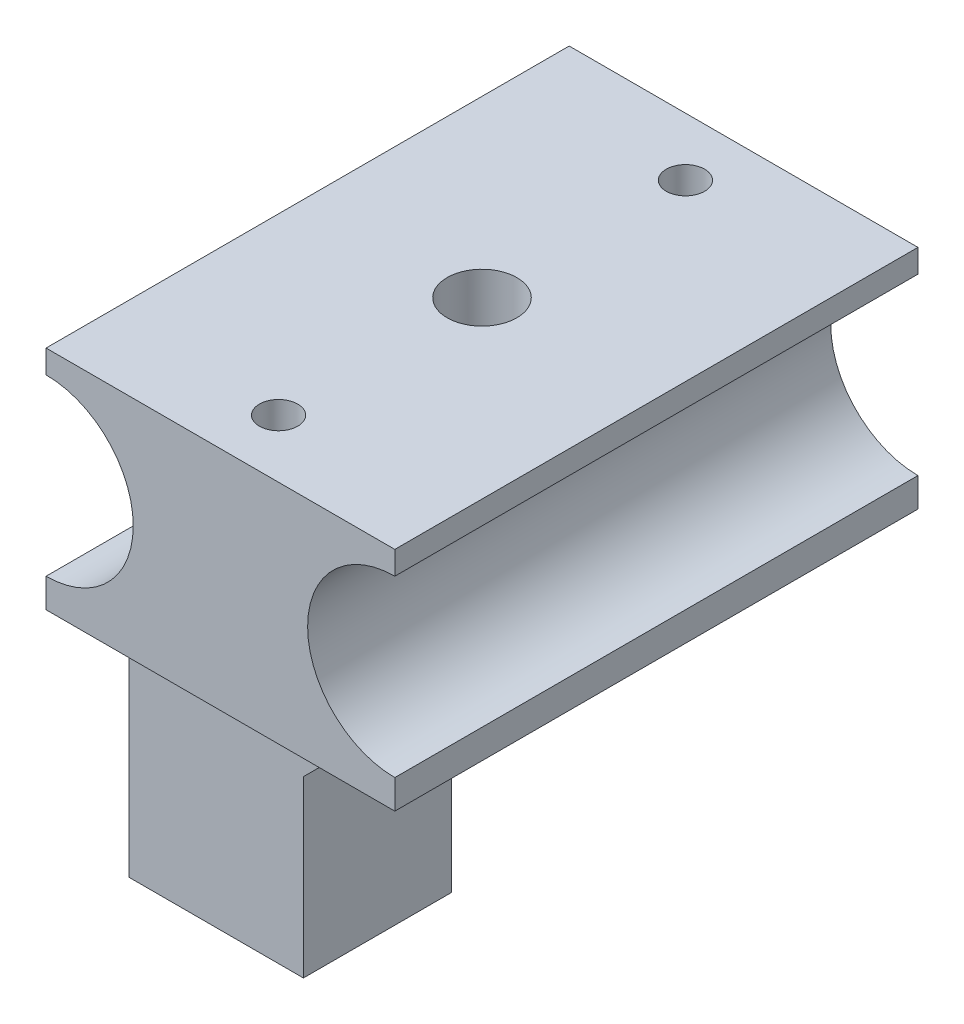
SolidWorks part; units mm, degrees
material "ABS"
ref_plane "Front Plane" through (0, 0, 0) normal (0, 0, 1) x (1, 0, 0)
ref_plane "Top Plane" through (0, 0, 0) normal (0, 1, 0) x (1, 0, 0)
ref_plane "Right Plane" through (0, 0, 0) normal (1, 0, 0) x (0, 0, -1)
sketch "Sketch1" plane through (0, 0, 0) normal (0, 0, 1) x (1, 0, 0)
  line L0 (15, 0) -> (-15, 0) construction
  line L5 (-15, 7.5) -> (-15, 9.5)
  line L6 (-15, 9.5) -> (15, 9.5)
  line L7 (15, 7.5) -> (15, 9.5)
  line L9 (-15, -7.5) -> (-15, -10)
  line L10 (-15, -10) -> (15, -10)
  line L11 (15, -7.5) -> (15, -10)
  arc A0 (15, 7.5) -> (15, -7.5) centre (15, 0) ccw
  arc A1 (-15, -7.5) -> (-15, 7.5) centre (-15, 0) ccw
  point P8 (0, 0)
  dimension "D2" = 15
  dimension "D1" = 30
  dimension "D3" = 2.5
  dimension "D4" = 2
extrude "Boss-Extrude1" add sketch "Sketch1" along normal mid plane 45
sketch "Sketch3" plane through (0, 0, 0) normal (0, 0, 1) x (1, 0, 0)
  line L0 (0, 9.5) -> (0, -10)
  line L1 (0, -10) -> (8, -10)
  line L2 (8, -10) -> (8, -3.25)
  line L3 (8, -3.25) -> (6, -3.25)
  line L4 (6, -3.25) -> (6, 2.75)
  line L5 (6, 2.75) -> (8, 2.75)
  line L6 (8, 2.75) -> (8, 9.5)
  line L7 (8, 9.5) -> (0, 9.5)
  line L8 (15, 9.5) -> (-15, 9.5) construction
  line L9 (-15, -10) -> (15, -10) construction
  dimension "D1" = 6
  dimension "D2" = 8
  dimension "D3" = 6
revolve "Cut-Revolve1" [suppressed] cut sketch "Sketch3" angle 360 about L0
hole_wizard "M4x0.7 Tapped Hole2" positions "Sketch5" profile "Sketch4" tap size "M4x0.7" standard "ANSI Metric" end condition through all
sketch "Sketch5" plane through (0, -10, 0) normal (0, -1, 0) x (-1, 0, 0)
  line L0 (0, 17.5) -> (0, -17.5) construction
  line L2 (15, -22.5) -> (-15, -22.5) construction
  point P0 (0, -17.5)
  point P2 (0, 17.5)
  dimension "D1" = 5
sketch "Sketch4" plane through (0, -10, 17.5) normal (1, 0, 0) x (0, 0, -1)
  line L0 (0, 0) -> (0, 19.5)
  line L1 (0, 19.5) -> (1.65, 19.5)
  line L2 (1.65, 19.5) -> (1.65, 0)
  line L5 (1.65, 0) -> (0, 0)
  line L11 (0, -6.35) -> (0, 107.95) construction
  dimension "Thru Tap Drill Dia." = 3.3
  dimension "Thru Tap Drill Depth" = 19.5
cosmetic thread "Hole Thread1" parameters "D2"=4
cosmetic thread "Hole Thread2" parameters "D2"=4
sketch "Sketch7" plane through (0, 0, 0) normal (0, 0, 1) x (1, 0, 0)
  line L0 (-15, -7.5) -> (-24, -7.5)
  line L1 (-24, -7.5) -> (-24, -42.5)
  line L5 (8.5, -10) -> (-15, -10)
  line L6 (-15, -10) -> (-15, -7.5)
  line L7 (-24, -42.5) -> (-9, -42.5)
  line L8 (-9, -42.5) -> (-9, -27.5)
  line L9 (-9, -27.5) -> (8.5, -10)
  dimension "D1" = 9
  dimension "D2" = 35
  dimension "D3" = 15
  dimension "D4" = 45
  dimension "D6" = 15
extrude "Boss-Extrude3" add sketch "Sketch7" against normal mid plane 12.725
hole_wizard "M4x0.7 Tapped Hole1" positions "Sketch9" profile "Sketch8" tap size "M4x0.7" standard "ANSI Metric"
sketch "Sketch9" plane through (-24, 0, 0) normal (1, 0, 0) x (0, 0, -1)
  line L0 (6.3625, -42.5) -> (-6.3625, -42.5) construction
  point P0 (0, -37.5)
  point P2 (0, -22.5)
  dimension "D1" = 15
  dimension "D2" = 5
sketch "Sketch8" plane through (-24, -37.5, 0) normal (0, 1, 0) x (0, 0, 1)
  line L0 (0, 0) -> (0, 10.9914)
  line L1 (0, 10.9914) -> (1.65, 10)
  line L2 (1.65, 10) -> (1.65, 0)
  line L5 (1.65, 0) -> (0, 0)
  line L10 (0, 10.9914) -> (-1.65, 10) construction
  line L11 (0, -6.35) -> (0, 107.95) construction
  dimension "Tap Drill Dia." = 3.3
  dimension "Tap Drill Depth" = 10
  dimension "Drill Angle" = 118
cosmetic thread "Hole Thread5" parameters "D1"=8, "D2"=4
cosmetic thread "Hole Thread6" parameters "D1"=8, "D2"=4
sketch "Sketch10" plane through (0, 0, -6.3625) normal (0, 0, -1) x (-1, 0, 0)
  line L0 (15, -10) -> (24, -19)
  line L1 (24, -7.5) -> (24, -42.5) construction
  line L2 (24, -19) -> (24, -7.5)
  line L3 (24, -7.5) -> (15, -7.5)
  line L4 (15, -7.5) -> (15, -10)
  dimension "D1" = 45
extrude "Cut-Extrude2" cut sketch "Sketch10" against normal blind 85
sketch "Sketch2" plane through (0, 9.5, 0) normal (0, 1, 0) x (1, 0, 0)
  circle A0 centre (0, 0) radius 3
  dimension "D1" = 6
extrude "Cut-Extrude1" cut sketch "Sketch2" against normal blind 50
